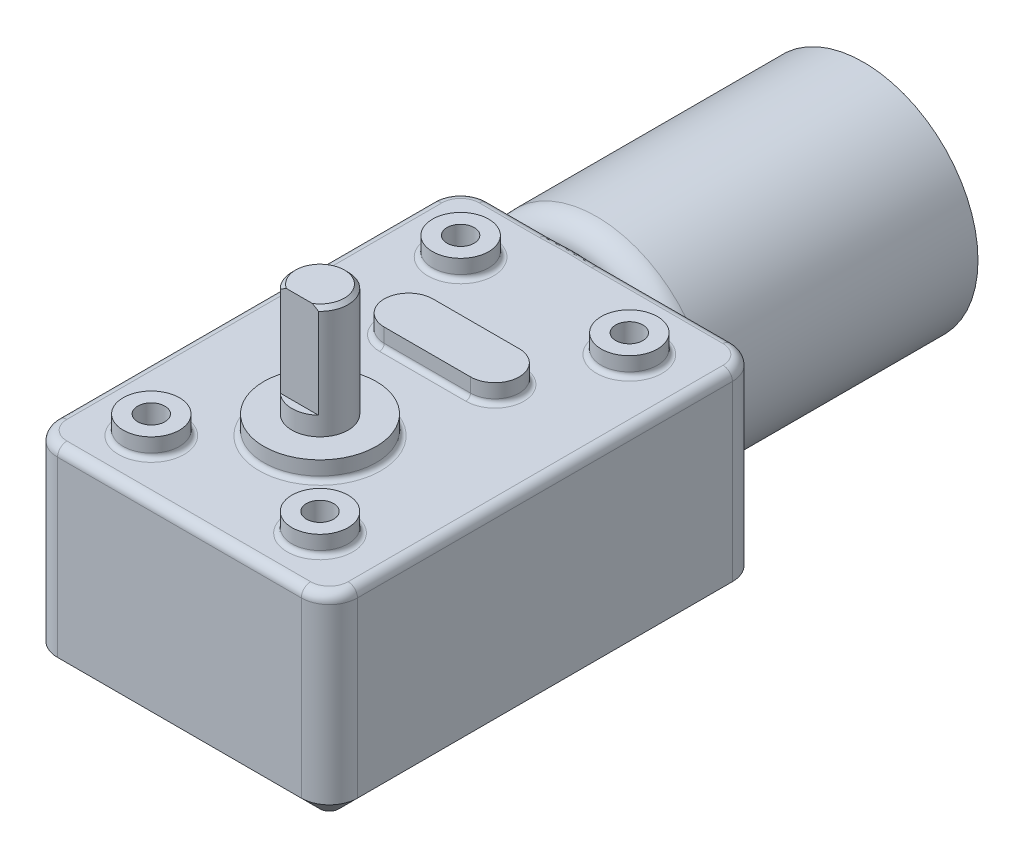
SolidWorks part; units mm, degrees
ref_plane "Front Plane" through (0, 0, 0) normal (0, 0, 1) x (1, 0, 0)
ref_plane "Top Plane" through (0, 0, 0) normal (0, 1, 0) x (1, 0, 0)
ref_plane "Right Plane" through (0, 0, 0) normal (1, 0, 0) x (0, 0, -1)
sketch "Sketch1" plane through (0, 0, 0) normal (0, 1, 0) x (1, 0, 0)
  line L0 (0, -15) -> (0, 31) construction
  line L1 (-13, -15) -> (13, -15)
  line L2 (-16, -12) -> (-16, 28)
  line L3 (-13, 31) -> (13, 31)
  line L4 (16, -12) -> (16, 28)
  circle A0 centre (0, 0) radius 3 construction
  circle A1 centre (-9, 24) radius 3 construction
  circle A2 centre (-9, -9) radius 3 construction
  circle A3 centre (9, -9) radius 3 construction
  circle A4 centre (9, 24) radius 3 construction
  arc A5 (-13, -15) -> (-16, -12) centre (-13, -12) cw
  arc A6 (13, -15) -> (16, -12) centre (13, -12) ccw
  arc A7 (-16, 28) -> (-13, 31) centre (-13, 28) cw
  arc A8 (13, 31) -> (16, 28) centre (13, 28) cw
  dimension "D4" = 6
  dimension "D5" = 6
  dimension "D7" = 3
  dimension "D8" = 3
  dimension "D1" = 33
  dimension "D2" = 9
  dimension "D3" = 7
  dimension "D6" = 9
  dimension "D9" = 46
  dimension "D10" = 32
extrude "Boss-Extrude1" add sketch "Sketch1" along normal blind 21.5
sketch "Sketch2" plane through (0, 21.5, 0) normal (0, 1, 0) x (1, 0, 0)
  circle A0 centre (0, 0) radius 3
extrude "Boss-Extrude2" add sketch "Sketch2" along normal blind 14
sketch "Sketch3" plane through (0, 35.5, 0) normal (0, 1, 0) x (1, 0, 0)
  line L0 (-2.0396, -2.2) -> (2.0396, -2.2)
  circle A0 centre (0, 0) radius 3 construction
  arc A1 (-2.0396, -2.2) -> (2.0396, -2.2) centre (0, 0) ccw
  dimension "D1" = 2.2
extrude "Cut-Extrude1" cut sketch "Sketch3" against normal blind 10
sketch "Sketch4" plane through (0, 21.5, 0) normal (0, 1, 0) x (1, 0, 0)
  line L0 (-4.6012, 14.0529) -> (4.6012, 14.0529) construction
  line L1 (-4.6012, 16.6529) -> (4.6012, 16.6529)
  line L2 (-4.6012, 11.4529) -> (4.6012, 11.4529)
  line L3 (0, -15) -> (0, 31) construction
  circle A0 centre (-9, 24) radius 3
  circle A1 centre (9, 24) radius 3
  circle A2 centre (9, -9) radius 3
  circle A3 centre (-9, -9) radius 3
  circle A4 centre (0, 0) radius 6
  arc A5 (-4.6012, 16.6529) -> (-4.6012, 11.4529) centre (-4.6012, 14.0529) ccw
  arc A6 (4.6012, 11.4529) -> (4.6012, 16.6529) centre (4.6012, 14.0529) ccw
  point P12 (0, 14.0529)
  dimension "D1" = 12
  dimension "D2" = 2.6
extrude "Boss-Extrude3" add sketch "Sketch4" along normal blind 2
ref_plane "Plane1" through (0, 11, 0) normal (0, 1, 0) x (1, 0, 0)
sketch "Sketch5" plane through (0, 11, 0) normal (0, 1, 0) x (1, 0, 0)
  line L0 (-3.8, 29.6479) -> (-3.8, 60.8) construction
  line L1 (-3.8, 31) -> (-13.7, 31)
  line L2 (-3.8, 31) -> (-3.8, 60.8)
  line L3 (-15.75, 61.8) -> (-16, 61.8)
  line L4 (-16, 33.3) -> (-16, 61.8)
  line L5 (-3.8, 61.8) -> (-3.8, 69.8) construction
  line L6 (-15.75, 61.8) -> (-15.75, 60.8)
  line L7 (-15.75, 60.8) -> (-7.3, 60.8)
  line L8 (-6.8, 61.3) -> (-6.8, 61.8)
  line L9 (-6.8, 61.8) -> (-5.3, 61.8)
  line L10 (-3.8, 60.8) -> (-3.8, 61.8)
  line L11 (-5.3, 61.8) -> (-5.3, 65.4)
  line L12 (-4.9, 65.8) -> (-3.8, 65.8)
  line L13 (-3.8, 61.8) -> (-3.8, 65.8)
  line L14 (-13, 31) -> (13, 31) construction
  line L15 (-16, -12) -> (-16, 28) construction
  line L16 (-5.3, 65.4) -> (-4.9, 65.8)
  arc A0 (-13.7, 31) -> (-16, 33.3) centre (-13.7, 33.3) cw
  arc A1 (-7.3, 60.8) -> (-6.8, 61.3) centre (-7.3, 61.3) ccw
  point P16 (-5.3, 65.8)
  dimension "D2" = 2.3
  dimension "D9" = 0.5
  dimension "D1" = 12.2
  dimension "D3" = 0.25
  dimension "D4" = 1
  dimension "D5" = 1.5
  dimension "D6" = 12.2
  dimension "D7" = 3
  dimension "D8" = 4
revolve "Revolve1" add sketch "Sketch5" angle 360 about L2
sketch "Sketch6" plane through (0, 11, 0) normal (0, 1, 0) x (1, 0, 0)
  line L0 (-10.27, 63.8239) -> (-10.27, 63.3236) construction
  line L1 (-11.27, 60.8) -> (-9.27, 60.8)
  line L2 (-11.27, 60.8) -> (-11.27, 63.8239)
  line L3 (-11.27, 63.8239) -> (-9.27, 63.8239) construction
  line L4 (-9.27, 60.8) -> (-9.27, 63.8239)
  line L5 (-9.8226, 63.8239) -> (-9.8226, 63.3236)
  line L6 (-10.7175, 63.8239) -> (-10.7175, 63.3236)
  line L7 (-3.8, 61.8) -> (-3.8, 72.427) construction
  line L8 (3.67, 63.8239) -> (1.67, 63.8239) construction
  line L9 (1.67, 60.8) -> (1.67, 63.8239)
  line L10 (3.67, 60.8) -> (3.67, 63.8239)
  line L11 (3.67, 60.8) -> (1.67, 60.8)
  line L12 (2.67, 63.8239) -> (2.67, 63.3236) construction
  line L13 (2.2226, 63.8239) -> (2.2226, 63.3236)
  line L14 (3.1175, 63.8239) -> (3.1175, 63.3236)
  line L20 (-15.75, 60.8) -> (-7.3, 60.8) construction
  arc A0 (-9.8226, 63.8239) -> (-10.7175, 63.8239) centre (-10.27, 63.8239) ccw
  arc A1 (-10.7175, 63.3236) -> (-9.8226, 63.3236) centre (-10.27, 63.3236) ccw
  arc A2 (1.67, 63.8239) -> (3.67, 63.8239) centre (2.67, 63.8239) cw
  arc A3 (-9.27, 63.8239) -> (-11.27, 63.8239) centre (-10.27, 63.8239) ccw
  arc A4 (2.2226, 63.8239) -> (3.1175, 63.8239) centre (2.67, 63.8239) cw
  arc A5 (3.1175, 63.3236) -> (2.2226, 63.3236) centre (2.67, 63.3236) cw
  point P6 (-10.27, 63.5737)
  point P20 (2.67, 63.5737)
  dimension "D1" = 2
extrude "Boss-Extrude4" add sketch "Sketch6" along normal blind 0.2 and the other way blind 0.2 separate body
fillet "Fillet1" radius 1 8 edges at (-15.1213, 21.5, 14.1213) (-16, 21.5, -8) (-15.1213, 21.5, -30.1213) (0, 21.5, -31) (15.1213, 21.5, -30.1213) (16, 21.5, -8) (15.1213, 21.5, 14.1213) (0, 21.5, 15)
chamfer "Chamfer1" distance 2 angle 45 8 edges at (0, 0, -31) (-15.1213, 0, -30.1213) (15.1213, 0, -30.1213) (-16, 0, -8) (16, 0, -8) (-15.1213, 0, 14.1213) (15.1213, 0, 14.1213) (0, 0, 15)
fillet "Fillet2" radius 0.5 9 edges at (0, 21.5, -11.4529) (-7.2012, 21.5, -14.0529) (0, 21.5, -16.6529) (0, 21.5, -6) (-9, 21.5, 6) (-9, 21.5, -27) (7.2012, 21.5, -14.0529) (9, 21.5, -27) (9, 21.5, 6)
hole_wizard "M3.5x0.6 Tapped Hole1" positions "Sketch8" profile "Sketch7" tap size "M3.5x0.6" standard "ANSI Metric"
sketch "Sketch8" plane through (0, 23.5, 0) normal (0, 1, 0) x (1, 0, 0)
  point P0 (-9, 24)
  point P3 (9, 24)
  point P6 (9, -9)
  point P9 (-9, -9)
sketch "Sketch7" plane through (-9, 23.5, -24) normal (1, 0, 0) x (0, 0, 1)
  line L0 (0, 0) -> (0, 7.8712)
  line L1 (0, 7.8712) -> (1.45, 7)
  line L2 (1.45, 7) -> (1.45, 0)
  line L5 (1.45, 0) -> (0, 0)
  line L10 (0, 7.8712) -> (-1.45, 7) construction
  line L11 (0, -6.35) -> (0, 107.95) construction
  dimension "Tap Drill Dia." = 2.9
  dimension "Tap Drill Depth" = 7
  dimension "Drill Angle" = 118
cosmetic thread "Hole Thread1" parameters "D1"=7, "D2"=3.5
cosmetic thread "Hole Thread2" parameters "D1"=7, "D2"=3.5
cosmetic thread "Hole Thread3" parameters "D1"=7, "D2"=3.5
cosmetic thread "Hole Thread4" parameters "D1"=7, "D2"=3.5
chamfer "Chamfer3" distance 0.4 angle 45 1 edges at (0, 35.5, -3)
sketch "Sketch11" plane through (0, 0, 0) normal (0, -1, 0) x (1, 0, 0)
  circle A0 centre (0, 0) radius 6.3267
extrude "Boss-Extrude5" add sketch "Sketch11" along normal blind 1
fillet "Fillet3" radius 0.3 1 edges at (0, 0, -6.3267)
